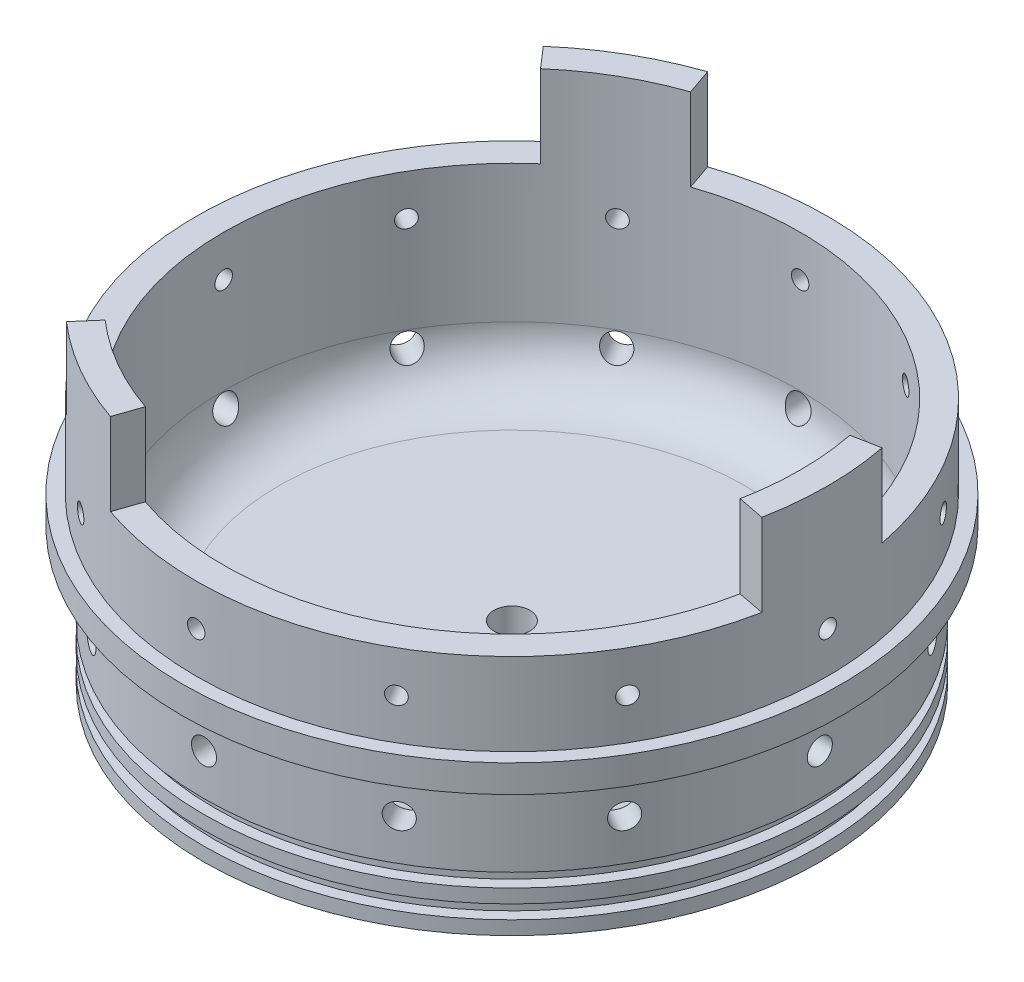
SolidWorks part; units mm, degrees
material "2024-T4"
ref_plane "Front Plane" through (0, 0, 0) normal (0, 0, 1) x (1, 0, 0)
ref_plane "Top Plane" through (0, 0, 0) normal (0, 1, 0) x (1, 0, 0)
ref_plane "Right Plane" through (0, 0, 0) normal (1, 0, 0) x (0, 0, -1)
sketch "Sketch1" plane through (0, 0, 0) normal (0, 1, 0) x (1, 0, 0)
  circle A0 centre (0, 0) radius 76.2
  dimension "D1" = 152.4
extrude "Center Ring(TotOD&Thk)" add sketch "Sketch1" along normal blind 6.35
sketch "Sketch2" plane through (0, 6.35, 0) normal (0, 1, 0) x (1, 0, 0)
  circle A0 centre (0, 0) radius 73.025
  dimension "D1" = 146.05
extrude "Top Ring(AcrylicID&Hgt)" add sketch "Sketch2" along normal blind 38.1
sketch "Sketch3" plane through (0, 0, 0) normal (0, -1, 0) x (1, 0, 0)
  circle A0 centre (0, 0) radius 71.247
  dimension "D1" = 142.494
extrude "Lower Ring(TankID&Depth)" add sketch "Sketch3" along normal blind 31.75
sketch "Sketch4" plane through (0, 44.45, 0) normal (0, 1, 0) x (1, 0, 0)
  circle A0 centre (0, 0) radius 66.675
  circle A1 centre (0, 0) radius 73.025 construction
  circle A2 centre (0, 0) radius 73.025
  dimension "D1" = 133.35
extrude "Bulkhead Hollow(UpperWall&BlkhdThk" cut sketch "Sketch4" against normal offset from surface (63.5 mm away) 12.7 contours A0 up to face at (0, -31.75, -71.247)
sketch "Sketch5" plane through (0, 0, 0) normal (0, 0, 1) x (1, 0, 0)
  line L0 (-71.247, 0) -> (-71.247, -31.75) construction
  line L1 (-71.247, 0) -> (-71.247, -31.75)
  line L2 (-71.247, -28.575) -> (-68.707, -28.575)
  line L3 (-68.707, -28.575) -> (-68.707, -25.4)
  line L4 (-68.707, -25.4) -> (-71.247, -25.4)
  line L5 (-71.247, -22.225) -> (-68.707, -22.225)
  line L6 (-68.707, -22.225) -> (-68.707, -19.05)
  line L7 (-68.707, -19.05) -> (-71.247, -19.05)
  line L8 (-71.247, -31.75) -> (71.247, -31.75) construction
  line L9 (0, 0) -> (0, -31.75) construction
  dimension "D1" = 2.54
  dimension "D2" = 3.175
  dimension "D3" = 3.175
  dimension "D4" = 3.175
  dimension "D5" = 3.175
revolve "O-Ring Channel" cut sketch "Sketch5" angle 360 about L9 region at (-69.977, -20.6375, 0) region at (-69.977, -26.9875, 0)
sketch "Sketch8" plane through (0, 0, 0) normal (0, 0, 1) x (1, 0, 0)
  circle A0 centre (0, -9.525) radius 2.8956
  dimension "D1" = 5.7912
  dimension "D2" = 9.525
extrude "Lower Bolt Hole (DrillDia&Dist)" cut sketch "Sketch8" along normal through all
pattern_circular "Lower Bolt Hole Ammount" count 12 over 360 about axis through (0, -31.75, 0) along (0, 1, 0) of "Lower Bolt Hole (DrillDia&Dist)" reverse direction yes
sketch "Sketch9" plane through (0, 0, 0) normal (0, 0, 1) x (1, 0, 0)
  line L0 (76.2, 6.35) -> (-76.2, 6.35) construction
  line L1 (76.2, 6.35) -> (-76.2, 6.35)
  circle A0 centre (0, 15.875) radius 2.0193
  dimension "D1" = 4.0386
  dimension "D2" = 9.525
extrude "Upper Bolt Hole (DrillDia&Dist)" cut sketch "Sketch9" against normal through all contours A0 region at (0, 15.875, 0)
pattern_circular "CirPattern1" count 12 over 360 about axis through (0, 44.45, 0) along (0, -1, 0) of "Upper Bolt Hole (DrillDia&Dist)"
fillet "Smoothing" radius 12.7 1 edges at (0, -19.05, -66.675)
sketch "Sketch10" plane through (0, 44.45, 0) normal (0, 1, 0) x (1, 0, 0)
  line L0 (65.4543, 12.7) -> (71.688, 13.9095)
  line L1 (65.4543, -12.7) -> (71.688, -13.9095)
  line L2 (-21.7286, -63.0351) -> (-23.798, -69.0384)
  line L3 (-43.7257, -50.3351) -> (-47.89, -55.1289)
  line L4 (-43.7257, 50.3351) -> (-47.89, 55.1289)
  line L5 (-21.7286, 63.0351) -> (-23.798, 69.0384)
  circle A0 centre (0, 0) radius 66.675 construction
  circle A1 centre (0, 0) radius 73.025
  circle A2 centre (0, 0) radius 73.025
  circle A3 centre (0, 0) radius 66.675
  point P20 (0, 0)
  circle M5 centre (0, 0) radius 66.675
  circle M6 centre (0, 0) radius 73.025
  dimension "D2" = 25.4
  dimension "D3" = 12.7
extrude "Cut-Extrude1" cut sketch "Sketch10" against normal blind 19.05 contours L5 L0 M5 M6 | L4 L3 M5 M6 | L2 L1 M5 M6 region at (33.9022, 44.45, -58.7204) region at (68.356, 44.45, 14.4135) region at (-67.8158, 44.45, 0)
sketch "Sketch11" plane through (0, -19.05, 0) normal (0, 1, 0) x (1, 0, 0)
  circle A0 centre (0, 0) radius 4.1672
  dimension "D1" = 8.3344
extrude "1/8NPTHole" cut sketch "Sketch11" against normal through all
equation "\"D4@Sketch5\"=\"D2@Sketch5\""
equation "\"D5@Sketch5\"=\"D3@Sketch5\""
equation "\"D3@Sketch10\"=\"D2@Sketch10\"/2"
